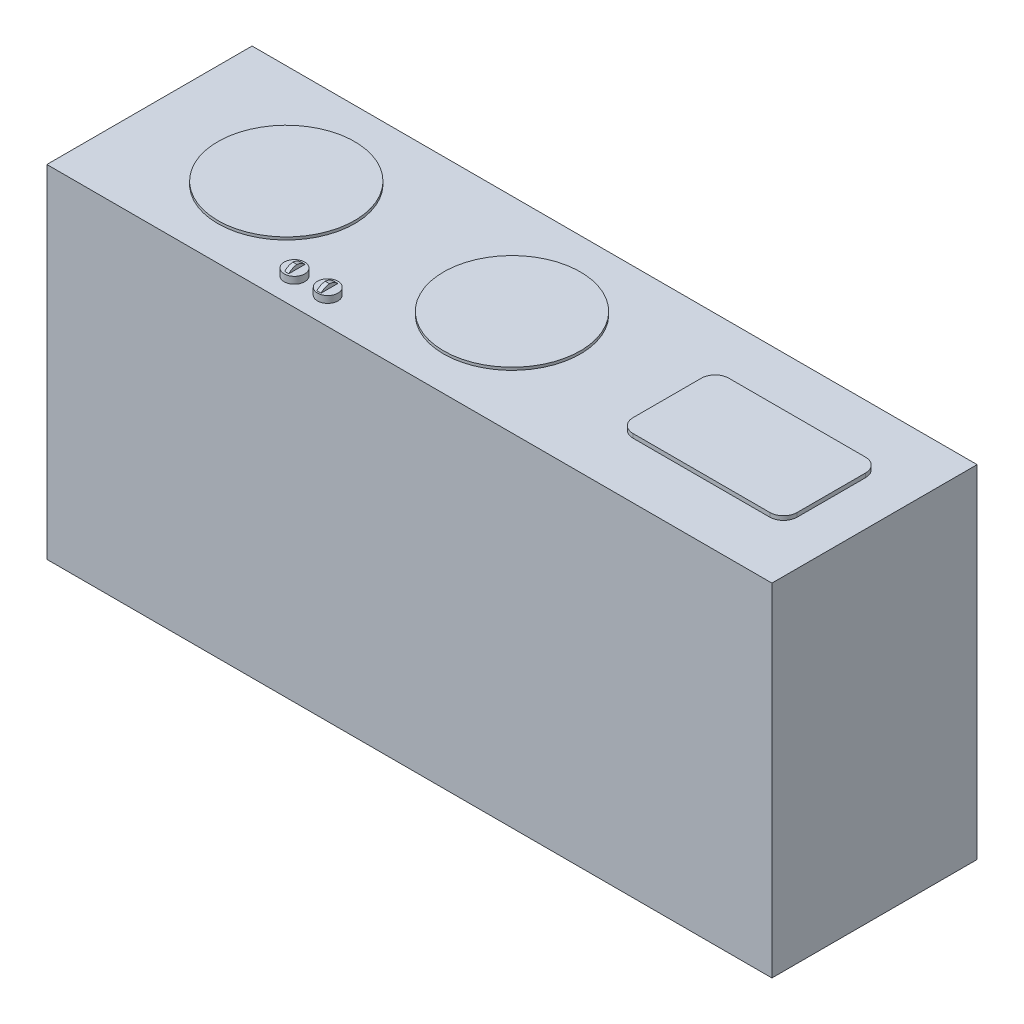
SolidWorks part; units mm, degrees
ref_plane "前基準面" through (0, 0, 0) normal (0, 0, 1) x (1, 0, 0)
ref_plane "上基準面" through (0, 0, 0) normal (0, 1, 0) x (1, 0, 0)
ref_plane "右基準面" through (0, 0, 0) normal (1, 0, 0) x (0, 0, -1)
sketch "草圖1" plane through (0, 0, 0) normal (0, 1, 0) x (1, 0, 0)
  line L1 (-26.5, 7.5) -> (26.5, 7.5)
  line L2 (-26.5, 7.5) -> (-26.5, -7.5)
  line L3 (-26.5, -7.5) -> (26.5, -7.5)
  line L4 (26.5, 7.5) -> (26.5, -7.5)
  line L5 (-26.5, 7.5) -> (26.5, -7.5) construction
  line L6 (-26.5, -7.5) -> (26.5, 7.5) construction
  point P0 (0, 0)
  dimension "D1" = 15
  dimension "D2" = 53
extrude "填料-伸長1" add sketch "草圖1" along normal blind 25
sketch "草圖2" plane through (0, 25, 0) normal (0, 1, 0) x (1, 0, 0)
  line L0 (-26.5, 0) -> (26.5, 0) construction
  line L1 (-26.5, 7.5) -> (-26.5, -7.5) construction
  line L2 (26.5, -7.5) -> (26.5, 7.5) construction
  circle A1 centre (0, 0) radius 5
  circle A2 centre (-16.5, 0) radius 5
  point P6 (-17.2012, 0)
  dimension "D1" = 10
  dimension "D2" = 10
  dimension "D3" = 10
extrude "填料-伸長2" add sketch "草圖2" along normal blind 0.2
sketch "草圖3" plane through (0, 25, 0) normal (0, 1, 0) x (1, 0, 0)
  line L0 (-9.1839, 7.5) -> (-9.1839, -7.5)
  line L1 (26.5, 7.5) -> (-26.5, 7.5) construction
  line L2 (-26.5, -7.5) -> (26.5, -7.5) construction
  circle A0 centre (-7.9682, -5.5008) radius 0.75
  circle A1 centre (-10.3997, -5.5008) radius 0.75
  point P6 (-12.6117, -8.4663)
  point P11 (0, 0)
  dimension "D1" = 1.5
extrude "填料-伸長4" add sketch "草圖3" along normal blind 0.5 contours A0 | A1 region at (-7.9682, 25, 5.5008) region at (-10.3997, 25, 5.5008)
sketch "草圖4" plane through (0, 25.5, 0) normal (0, 1, 0) x (1, 0, 0)
  line L1 (-8.1405, -6.1269) -> (-7.8325, -6.1269)
  line L2 (-8.1405, -6.1269) -> (-8.1405, -4.8992)
  line L3 (-8.1405, -4.8992) -> (-7.8325, -4.8992)
  line L4 (-7.8325, -6.1269) -> (-7.8325, -4.8992)
  point P4 (-12.8269, -7.709)
extrude "填料-伸長5" add sketch "草圖4" along normal blind 0.3
sketch "草圖6" plane through (0, 25.5, 0) normal (0, 1, 0) x (1, 0, 0)
  line L1 (-10.5403, -6.077) -> (-10.2394, -6.077)
  line L2 (-10.5403, -6.077) -> (-10.5403, -4.8858)
  line L3 (-10.5403, -4.8858) -> (-10.2394, -4.8858)
  line L4 (-10.2394, -6.077) -> (-10.2394, -4.8858)
extrude "填料-伸長8" add sketch "草圖6" along normal blind 0.3
sketch "草圖8" plane through (0, 25, 0) normal (0, 1, 0) x (1, 0, 0)
  line L1 (11.2507, 3.5947) -> (23.2507, 3.5947)
  line L2 (11.2507, 3.5947) -> (11.2507, -3.4053)
  line L3 (11.2507, -3.4053) -> (23.2507, -3.4053)
  line L4 (23.2507, 3.5947) -> (23.2507, -3.4053)
  line L5 (11.2507, 3.5947) -> (23.2507, -3.4053) construction
  line L6 (11.2507, -3.4053) -> (23.2507, 3.5947) construction
  point P0 (17.2507, 0.0947)
  dimension "D1" = 12
  dimension "D2" = 7
extrude "填料-伸長9" add sketch "草圖8" along normal blind 0.3
fillet "圓角1" radius 1 4 edges at (11.2507, 25.15, 3.4053) (11.2507, 25.15, -3.5947) (23.2507, 25.15, -3.5947) (23.2507, 25.15, 3.4053)
fillet "圓角2" radius 1 4 edges at (-10.3899, 25.8, 4.8858) (-10.3899, 25.8, 6.077) (-7.9865, 25.8, 6.1269) (-7.9865, 25.8, 4.8992)
